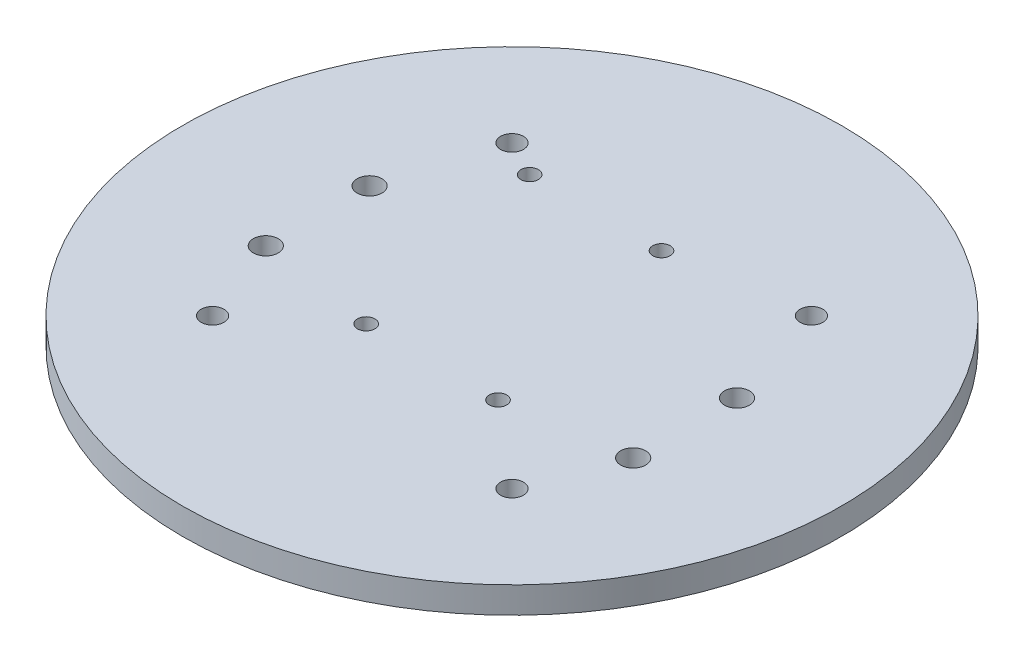
SolidWorks part; units mm, degrees
other "Markup1"
sketch "Sketch21" plane through (-65.5, -15.05, -60) normal (-0.0927, -0.2854, -0.9539) x (0.9951, -0.0609, -0.0785)
material "6061 Alloy"
ref_plane "Front Plane" through (0, 0, 0) normal (0, 0, 1) x (1, 0, 0)
ref_plane "Top Plane" through (0, 0, 0) normal (0, 1, 0) x (1, 0, 0)
ref_plane "Right Plane" through (0, 0, 0) normal (1, 0, 0) x (0, 0, -1)
sketch "Sketch1" plane through (0, 0, 0) normal (0, 1, 0) x (1, 0, 0)
  circle A0 centre (0, 0) radius 79.375
  dimension "D1" = 158.75
extrude "Boss-Extrude1" add sketch "Sketch1" along normal mid plane 6.35
sketch "Sketch2" plane through (0, -3.175, 0) normal (0, -1, 0) x (1, 0, 0)
  circle A0 centre (0, 0) radius 12.065
  circle A1 centre (0, 0) radius 79.375 construction
  dimension "D1" = 24.13
sketch "Sketch5" plane through (0, 3.175, 0) normal (0, 1, 0) x (1, 0, 0)
  circle A0 centre (0, 0) radius 10.4
  circle A1 centre (0, 0) radius 79.375 construction
  dimension "D1" = 20.8
hole_wizard "Tap Drill for M5x0.8 Tap1" positions "Sketch22" profile "Sketch23" hole size "M5x0.8" standard "ANSI Metric" end condition through all
sketch "Sketch22" plane through (0, 3.175, 0) normal (0, 1, 0) x (1, 0, 0)
  point P0 (-27.3188, 31.5712)
  point P3 (4.4312, 31.5712)
  point P6 (-15.875, -19.2459)
  point P9 (15.875, -19.2459)
  dimension "D1" = 31.75
  dimension "D2" = 31.5712
  dimension "D3" = 4.4312
  dimension "D4" = 31.75
  dimension "D5" = 19.2459
  dimension "D6" = 15.875
sketch "Sketch23" plane through (-27.3188, 3.175, -31.5712) normal (1, 0, 0) x (0, 0, 1)
  line L0 (0, 0) -> (0, 6.35)
  line L1 (0, 6.35) -> (2.1, 6.35)
  line L2 (2.1, 6.35) -> (2.1, 0)
  line L5 (2.1, 0) -> (0, 0)
  line L11 (0, -6.35) -> (0, 107.95) construction
  dimension "Thru Hole Dia." = 4.2
  dimension "Thru Hole Depth" = 6.35
hole_wizard "Tap Drill for M7x1.0 Tap1" positions "Sketch24" profile "Sketch25" hole size "M7x1.0" standard "ANSI Metric" end condition through all
sketch "Sketch24" plane through (0, 3.175, 0) normal (0, 1, 0) x (1, 0, 0)
  point P0 (-44.245, 9.9416)
  point P3 (-44.245, -15.0584)
  point P6 (44.245, 9.9416)
  point P9 (44.245, -15.0584)
  dimension "D1" = 25
  dimension "D2" = 44.245
  dimension "D3" = 9.9416
  dimension "D4" = 25
  dimension "D5" = 44.245
  dimension "D6" = 15.0584
sketch "Sketch25" plane through (-44.245, 3.175, -9.9416) normal (1, 0, 0) x (0, 0, 1)
  line L0 (0, 0) -> (0, 6.35)
  line L1 (0, 6.35) -> (3, 6.35)
  line L2 (3, 6.35) -> (3, 0)
  line L5 (3, 0) -> (0, 0)
  line L11 (0, -6.35) -> (0, 107.95) construction
  dimension "Thru Hole Dia." = 6
  dimension "Thru Hole Depth" = 6.35
sketch "Sketch28" plane through (0, 3.175, 0) normal (0, 1, 0) x (1, 0, 0)
  circle A0 centre (0, 0) radius 51
  circle A1 centre (35.8572, -36.2665) radius 4.2952
  dimension "D1" = 102
hole_wizard "M5 Clearance Hole1" positions "Sketch29" profile "Sketch30" hole size "M5" standard "ANSI Metric" end condition through all
sketch "Sketch29" plane through (0, 3.175, 0) normal (0, 1, 0) x (1, 0, 0)
  line L0 (-36.0624, 36.0624) -> (-36.0624, -36.0624) construction
  line L2 (-36.0624, 36.0624) -> (36.0624, 36.0624) construction
  line L3 (36.0624, 36.0624) -> (36.0624, -36.0624) construction
  line L4 (36.0624, -36.0624) -> (-36.0624, -36.0624) construction
  circle A0 centre (0, 0) radius 51 construction
  point P0 (-36.0624, 36.0624)
  point P4 (-36.0624, -36.0624)
  point P6 (36.0624, -36.0624)
  point P8 (36.0624, 36.0624)
sketch "Sketch30" plane through (-36.0624, 3.175, -36.0624) normal (1, 0, 0) x (0, 0, 1)
  line L0 (0, 0) -> (0, 6.35)
  line L1 (0, 6.35) -> (2.75, 6.35)
  line L2 (2.75, 6.35) -> (2.75, 0)
  line L5 (2.75, 0) -> (0, 0)
  line L11 (0, -6.35) -> (0, 107.95) construction
  dimension "Thru Hole Dia." = 5.5
  dimension "Thru Hole Depth" = 6.35
